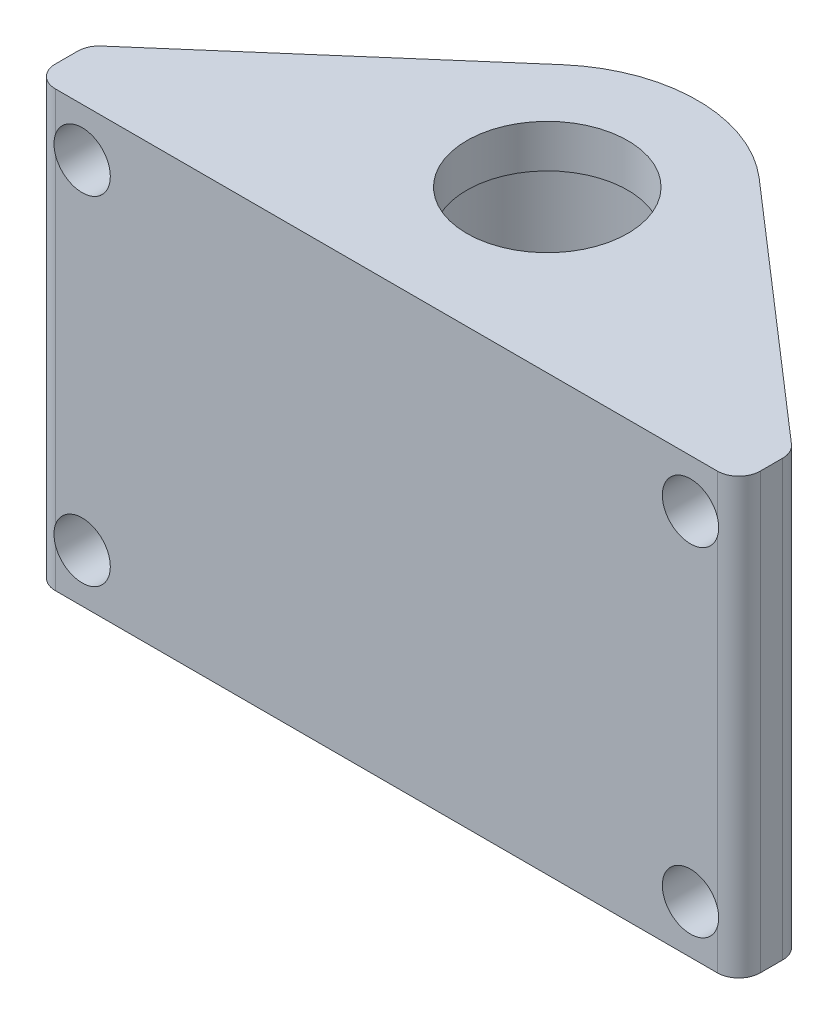
SolidWorks part; units mm, degrees
ref_plane "Alzado" through (0, 0, 0) normal (0, 0, 1) x (1, 0, 0)
ref_plane "Planta" through (0, 0, 0) normal (0, 1, 0) x (1, 0, 0)
ref_plane "Vista lateral" through (0, 0, 0) normal (1, 0, 0) x (0, 0, -1)
sketch "Croquis2" plane through (0, 0, 0) normal (0, 1, 0) x (1, 0, 0)
  line L0 (41.7195, 0) -> (-41.7195, 0)
  line L1 (-41.7195, 0) -> (-41.7195, 6.35)
  line L2 (-41.7195, 6.35) -> (-11.6628, 32.4704)
  line L3 (0, 0) -> (0, 19.05) construction
  line L4 (41.7195, 6.35) -> (11.6628, 32.4704)
  line L5 (41.7195, 0) -> (41.7195, 6.35)
  line L6 (-41.7195, 6.35) -> (41.7195, 6.35) construction
  arc A0 (-11.6628, 32.4704) -> (0, 36.83) centre (0, 19.05) cw
  arc A1 (11.6628, 32.4704) -> (0, 36.83) centre (0, 19.05) ccw
  circle A2 centre (0, 19.05) radius 12.7
  circle A3 centre (0, 19.05) radius 9.525
  dimension "D1" = 25.4
  dimension "D5" = 19.05
  dimension "D2" = 83.439
  dimension "D3" = 6.35
  dimension "D4" = 5.08
extrude "Saliente-Extruir1" add sketch "Croquis2" against normal blind 51.435 contours L4 A1 A0 L2 L1 L0 L5 A2 | A2 A3 region at (0, 0, -0.9121) region at (-12.3408, 0, -19.05)
sketch "Croquis3" plane through (0, 0, 0) normal (0, 1, 0) x (1, 0, 0)
  circle A0 centre (0, 19.05) radius 12.7 construction
  circle A1 centre (0, 19.05) radius 12.7
extrude "Cortar-Extruir1" cut sketch "Croquis3" against normal through all from offset 5.08 offset against normal yes
sketch "Croquis4" plane through (0, 0, 0) normal (0, 0, 1) x (1, 0, 0)
  line L0 (0, 0) -> (0, -51.435) construction
  line L1 (41.7195, 0) -> (-41.7195, 0) construction
  line L2 (41.7195, -51.435) -> (-41.7195, -51.435) construction
  line L3 (-41.7195, -25.7175) -> (41.7195, -25.7175) construction
  line L4 (-41.7195, -51.435) -> (-41.7195, 0) construction
  line L5 (41.7195, -51.435) -> (41.7195, 0) construction
  circle A0 centre (-36, -5.7175) radius 3.3337
  circle A2 centre (36, -5.7175) radius 3.3337
  circle A3 centre (36, -45.7175) radius 3.3337
  circle A4 centre (-36, -45.7175) radius 3.3337
  dimension "D1" = 6.6675
  dimension "D2" = 72
  dimension "D3" = 40
extrude "Saliente-Extruir3" add sketch "Croquis4" against normal blind 6.35
extrude "Cortar-Extruir3" cut sketch "Croquis4<2>" against normal through all contours A0 | A2 | A3 | A4 region at (-36, -5.7175, 0) region at (36, -5.7175, 0) region at (36, -45.7175, 0) region at (-36, -45.7175, 0)
sketch "Croquis4<2>" plane through (0, 0, 0) normal (0, 0, 1) x (1, 0, 0) same geometry as "Croquis4"
fillet "Redondeo3" radius 2.54 4 edges at (41.7195, -25.7175, -6.35) (-41.7195, -25.7175, -6.35) (-41.7195, -25.7175, 0) (41.7195, -25.7175, 0)
